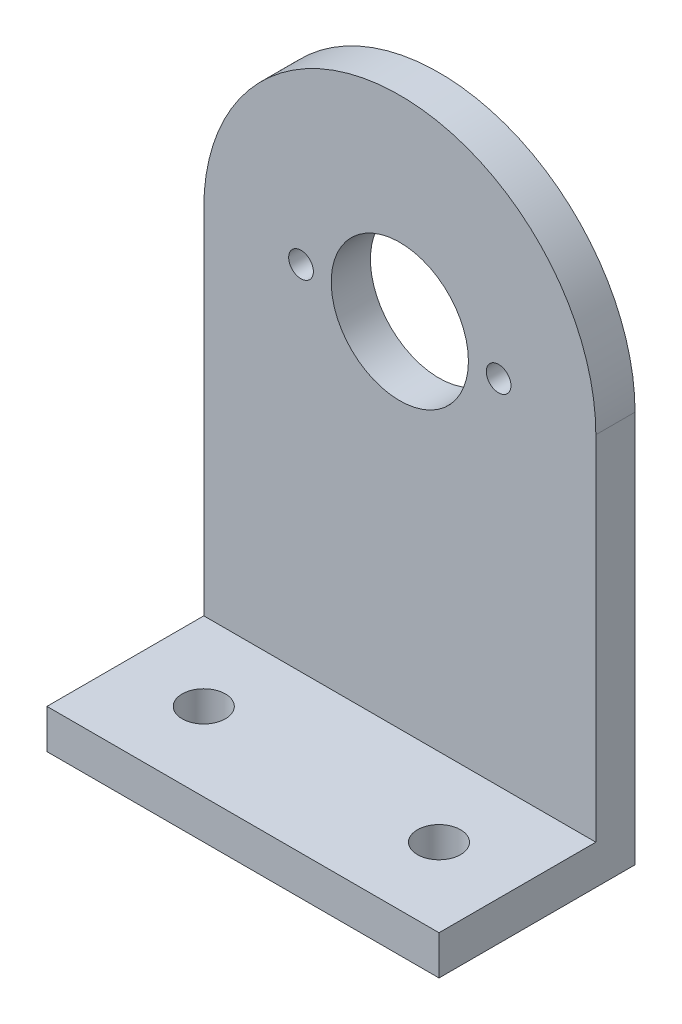
SolidWorks part; units mm, degrees
ref_plane "Front Plane" through (0, 0, 0) normal (0, 0, 1) x (1, 0, 0)
ref_plane "Top Plane" through (0, 0, 0) normal (0, 1, 0) x (1, 0, 0)
ref_plane "Right Plane" through (0, 0, 0) normal (1, 0, 0) x (0, 0, -1)
sketch "Sketch1" plane through (0, 0, 0) normal (0, 0, 1) x (1, 0, 0)
  line L1 (-15.875, 0) -> (15.875, 0)
  line L2 (-15.875, 0) -> (-15.875, -31.75)
  line L3 (-15.875, -31.75) -> (15.875, -31.75)
  line L4 (15.875, 0) -> (15.875, -31.75)
  circle A0 centre (0, 0) radius 15.875
  arc A2 (-15.875, 0) -> (15.875, 0) centre (0, 0) ccw
  dimension "D1" = 31.75
  dimension "D2" = 31.75
extrude "Boss-Extrude1" add sketch "Sketch1" along normal blind 3.175 contours A0 | L2 L1 L4 L3
sketch "Sketch3" plane through (0, 0, 3.175) normal (0, 0, 1) x (1, 0, 0)
  circle A0 centre (0, 0) radius 5.5562
  dimension "D1" = 11.1125
extrude "Cut-Extrude1" cut sketch "Sketch3" against normal through all
sketch "Sketch4" plane through (0, 0, 3.175) normal (0, 0, 1) x (1, 0, 0)
  line L0 (15.875, 0) -> (15.875, -31.75) construction
  line L1 (-15.875, -31.75) -> (15.875, -31.75)
  line L2 (-15.875, -31.75) -> (-15.875, -28.575)
  line L3 (-15.875, -28.575) -> (15.875, -28.575)
  line L4 (15.875, -31.75) -> (15.875, -28.575)
  dimension "D1" = 3.175
extrude "Boss-Extrude2" add sketch "Sketch4" along normal blind 12.7
sketch "Sketch5" plane through (0, -28.575, 0) normal (0, 1, 0) x (1, 0, 0)
  line L0 (-15.875, -9.525) -> (15.875, -9.525) construction
  line L1 (-15.875, -15.875) -> (-15.875, -3.175) construction
  line L2 (15.875, -15.875) -> (15.875, -3.175) construction
  line L3 (0, -3.175) -> (0, -15.875) construction
  line L4 (15.875, -3.175) -> (-15.875, -3.175) construction
  line L5 (15.875, -15.875) -> (-15.875, -15.875) construction
  circle A0 centre (-9.525, -9.525) radius 1.75
  circle A1 centre (9.525, -9.525) radius 1.75
  dimension "D1" = 3.5
  dimension "D2" = 9.525
extrude "Cut-Extrude2" cut sketch "Sketch5" against normal through all
hole_wizard "Ø2.0mm Dowel Hole1" positions "Sketch8" profile "Sketch9" hole size "Ø2.0" standard "ANSI Metric"
sketch "Sketch8" plane through (0, 0, 3.175) normal (0, 0, 1) x (1, 0, 0)
  line L0 (-15.875, 0) -> (15.875, 0) construction
  point P0 (-8.001, 0)
  point P2 (8.001, 0)
  dimension "D1" = 16.002
  dimension "D2" = 8.001
sketch "Sketch9" plane through (-8.001, 0, 3.175) normal (1, 0, 0) x (0, -1, 0)
  line L0 (0, 0) -> (0, 13.3009)
  line L1 (0, 13.3009) -> (1, 12.7)
  line L2 (1, 12.7) -> (1, 0)
  line L5 (1, 0) -> (0, 0)
  line L10 (0, 13.3009) -> (-1, 12.7) construction
  line L11 (0, -6.35) -> (0, 107.95) construction
  dimension "Hole Dia." = 2
  dimension "Hole Depth" = 12.7
  dimension "Drill Angle" = 118
